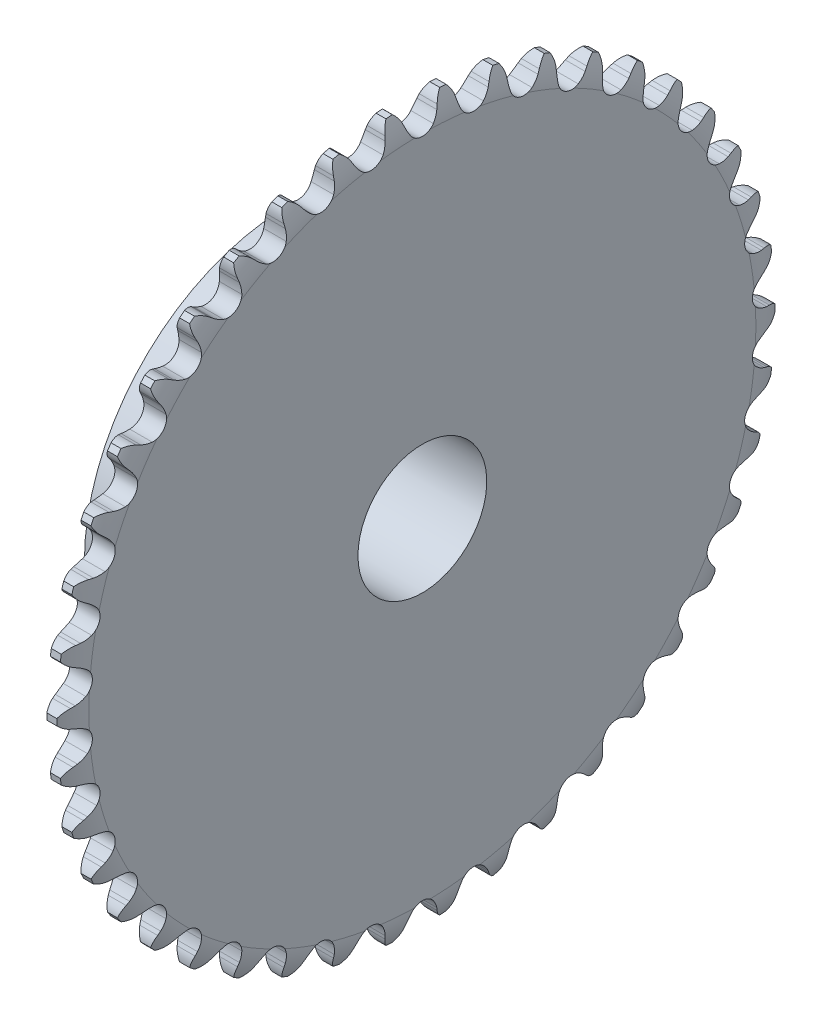
SolidWorks part; units mm, degrees
ref_plane "Plane1" through (0, 0, 0) normal (0, 0, 1) x (1, 0, 0)
ref_plane "Plane2" through (0, 0, 0) normal (0, 1, 0) x (1, 0, 0)
ref_plane "Plane3" through (0, 0, 0) normal (1, 0, 0) x (0, 0, -1)
sketch "Clipboard" plane through (0, 0, 0) normal (0, 1, 0) x (1, 0, 0)
  line L0 (0, 0) -> (4.719, -4.249)
  line L1 (-15, 0) -> (100, 0) construction
  line L2 (0, 0) -> (-0.5218, 0.5897)
  line L3 (0, 0) -> (-2.9658, 1.1335)
  line L4 (0, 0) -> (2.3595, 2.1245)
  line L5 (0, 0) -> (-15.2311, -5.6808)
  line L6 (0, 0) -> (-2.3214, -1.5662)
  line L7 (-0.5218, 0.5897) -> (11.3674, 11.6765)
  line L8 (-76.2, 38.1) -> (-58.1914, 38.1)
  line L9 (-73.2057, 38.5609) -> (-73.0533, 38.5634)
  line L10 (-73.0533, 76.1892) -> (-66.6525, 76.1892)
  circle A0 centre (0, 0) radius 1.651
  circle A1 centre (0, 0) radius 25.4
  circle A2 centre (0, 0) radius 25.4
  dimension "Dr" = 3.302
  dimension "MHD" = 50.8
  dimension "Hub_dia" = 50.8
  dimension "Num_teeth" = 42
  dimension "Pitch" = 6.35
  dimension "Width" = 3.175
  dimension "Chamfer_wid" = 0.7874
  dimension "Chamfer_dep" = 3.175
  dimension "Overall_len" = 16.256
  dimension "Show_teeth" = 42
  dimension "Thickness" = 2.8004
  dimension "OAL" = 16.2564
  dimension "T_dim" = 18.0086
  dimension "Width_const" = 0.1524
  dimension "Width_factor" = 0.93
  dimension "Num_strands" = 1
  dimension "Transv_pitch" = 6.4008
sketch "BasProSke" plane through (0, 0, 0) normal (0, 1, 0) x (1, 0, 0)
  line L0 (-10, 0) -> (60, 0) construction
  line L1 (0, 0) -> (0, 41.0974)
  line L2 (0, 0) -> (2.8003, 0)
  line L3 (2.8003, 0) -> (2.8004, 41.0974)
  line L4 (2.0129, 44.2724) -> (0.7874, 44.2724)
  arc A0 (0, 41.0974) -> (0.7874, 44.2724) centre (6.7949, 41.0974) cw
  arc A1 (2.8004, 41.0974) -> (2.0129, 44.2724) centre (-3.9946, 41.0974) ccw
  dimension "D1" = 6.7949
  dimension "G1" = 0.7874
  dimension "G2" = 0.7874
  dimension "H2" = 3.175
  dimension "Diameter" = 88.5449
  dimension "H1" = 3.175
  dimension "Thickness" = 2.8004
revolve "Base-Revolve" add sketch "BasProSke" angle 360 about L0
sketch "GrvSke" plane through (0, 0, 0) normal (0, 1, 0) x (1, 0, 0)
  line L0 (2.8003, 41.0974) -> (2.8003, 38.8114)
  line L1 (2.8003, 38.8114) -> (6.4008, 38.8114)
  line L2 (6.4008, 38.8114) -> (6.4008, 41.0974)
  line L3 (2.0129, 44.2724) -> (7.1882, 44.2724)
  line L4 (4.6006, 0) -> (4.6006, 52.07) construction
  line L5 (-10, 0) -> (60, 0) construction
  line L6 (0, 0) -> (35.56, 0) construction
  arc A0 (6.4008, 41.0974) -> (7.1882, 44.2724) centre (13.1957, 41.0974) cw
  arc A1 (2.8003, 41.0974) -> (2.0129, 44.2724) centre (-3.9946, 41.0974) ccw
  dimension "Diameter" = 88.5449
  dimension "H1" = 3.175
  dimension "Grv_diam" = 77.6229
  dimension "Grv_width" = 3.6004
  dimension "Offset" = 4.6006
  dimension "G1" = 0.7874
revolve "Groove" [suppressed] cut sketch "GrvSke" angle 360 about L6
pattern_linear "Grooves" [suppressed]
sketch "TooCutSke" plane through (0, 0, 0) normal (1, 0, 0) x (0, 0, -1)
  line L0 (1.958, 42.5878) -> (2.1189, 43.0357)
  line L1 (0, 0) -> (0, 107) construction
  line L2 (0, 42.4862) -> (-10, 42.4862) construction
  line L3 (-1.958, 42.5878) -> (-2.1189, 43.0357)
  arc A0 (1.3657, 41.4783) -> (1.958, 42.5878) centre (-2.1254, 44.0549) ccw
  arc A1 (1.3657, 41.4783) -> (-1.3657, 41.4783) centre (0, 42.4862) cw
  arc A2 (2.1189, 43.0357) -> (4.6099, 44.7876) centre (4.6099, 42.1408) cw
  arc A3 (-1.3657, 41.4783) -> (-1.958, 42.5878) centre (2.1254, 44.0549) cw
  arc A4 (-2.1189, 43.0357) -> (-4.6099, 44.7876) centre (-4.6099, 42.1408) ccw
  arc A5 (4.6099, 44.7876) -> (-4.6099, 44.7876) centre (0, 0) ccw
  dimension "R" = 1.6974
  dimension "E" = 4.339
  dimension "F" = 2.6469
  dimension "Pitch_radius" = 42.4862
  dimension "W" = 4.6099
  dimension "V" = 0.3455
  dimension "A" = 36.429
  dimension "B" = 16.667
extrude "ToothCut" cut sketch "TooCutSke" along normal through all
pattern_circular "TeethCuts" count 42 every 8.571 about axis through (-10, 0, 0) along (1, 0, 0) of "ToothCut"
sketch "HubNeaOneSke" plane through (0, 0, 0) normal (-1, 0, 0) x (0, 0, 1)
  circle A0 centre (0, 0) radius 25.4
  dimension "Diameter" = 50.8
extrude "HubNearOne" add sketch "HubNeaOneSke" along normal blind 13.456
sketch "HubNeaBotSke" plane through (0, 0, 0) normal (-1, 0, 0) x (0, 0, 1)
  circle A0 centre (0, 0) radius 25.4
  dimension "Diameter" = 50.8
extrude "HubNearBoth" [suppressed] add sketch "HubNeaBotSke" along normal blind 6.728
ref_plane "FarPln" through (2.8004, 0, 0) normal (1, 0, 0) x (0, 0, -1)
sketch "HubFarSke" plane through (2.8004, 0, 0) normal (1, 0, 0) x (0, 0, -1)
  circle A0 centre (0, 0) radius 25.4
  dimension "Diameter" = 50.8
extrude "HubFar" [suppressed] add sketch "HubFarSke" along normal blind 6.728
sketch "BorSke" plane through (0, 0, 0) normal (1, 0, 0) x (0, 0, -1)
  circle A0 centre (0, 0) radius 7.9375
  dimension "Diameter" = 15.875
extrude "Bore" cut sketch "BorSke" along normal mid plane 32.5127
sketch "KeySke" plane through (0, 0, 0) normal (1, 0, 0) x (0, 0, -1)
  line L0 (-2.3813, 0) -> (-2.3813, 10.0711)
  line L1 (-2.3813, 10.0711) -> (2.3813, 10.0711)
  line L2 (2.3813, 10.0711) -> (2.3813, 0)
  line L3 (0, 0) -> (0, 34) construction
  line L4 (-2.3813, 0) -> (2.3813, 0)
  dimension "Offset" = 10.0711
  dimension "Width" = 4.7625
extrude "Keyway" [suppressed] cut sketch "KeySke" along normal mid plane 32.5127
pattern_circular "Keyway2" [suppressed] count 2 every 90 about axis through (-10, 0, 0) along (1, 0, 0)
equation "\"Num_teeth@Clipboard\" = int( \"Num_teeth@Clipboard\" )"
equation "\"Num_teeth@Clipboard\" = ((sgn( \"Num_teeth@Clipboard\" - 5.0)+1)*( \"Num_teeth@Clipboard\" - 5.0))/2 +5.0"
equation "\"Num_teeth@Clipboard\" = ((sgn( \"Num_teeth@Clipboard\" - 200.0)-1)*( \"Num_teeth@Clipboard\" - 200.0))/-2 +200.0"
equation "\"MHD@Clipboard\" = \"Pitch@Clipboard\" * (1.0 / tan(3.14159265 / \"Num_teeth@Clipboard\" ) - 1.0) - 0.03"
equation "\"Thickness@Clipboard\"  = \"Width@Clipboard\" * \"Width_factor@Clipboard\" - \"Width_const@Clipboard\" + (\"Num_strands@Clipboard\" - 1) * \"Transv_pitch@Clipboard\""
equation "\"OAL@Clipboard\" = \"Thickness@Clipboard\""
equation "\"MHD@Clipboard\" = ((sgn( \"MHD@Clipboard\" - \"Hub_dia@Clipboard\" )-1)*( \"MHD@Clipboard\" - \"Hub_dia@Clipboard\" ))/-2+ \"Hub_dia@Clipboard\""
equation "\"OAL@Clipboard\" = ((sgn( \"OAL@Clipboard\" - \"Overall_len@Clipboard\" )+1)*( \"OAL@Clipboard\" - \"Overall_len@Clipboard\" ))/2 + \"Overall_len@Clipboard\" + 0.000002"
equation "\"Num_teeth@TeethCuts\" = int( \"Show_teeth@Clipboard\" ) + 1"
equation "\"Num_teeth@TeethCuts\" = ((sgn( \"Num_teeth@TeethCuts\" - \"Num_teeth@Clipboard\" )-1)*( \"Num_teeth@TeethCuts\" - \"Num_teeth@Clipboard\" ))/-2+ \"Num_teeth@Clipboard\""
equation "\"Num_teeth@TeethCuts\" = ((sgn( \"Num_teeth@TeethCuts\" - 2.0)+1)*( \"Num_teeth@TeethCuts\" - 2.0))/2 +2.0"
equation "\"Angle@TeethCuts\" = 360.0 / \"Num_teeth@Clipboard\""
equation "\"Pitch_radius@TooCutSke\" = ( \"Pitch@Clipboard\" / 2.0) / sin(3.14159265 / \"Num_teeth@Clipboard\" )  'ma"
equation "\"R@TooCutSke\"  = \"Dr@Clipboard\" * 0.5025 + 0.0015"
equation "\"A@TooCutSke\" = 35.0 + (60.0 / \"Num_teeth@Clipboard\")"
equation "\"E@TooCutSke\"  = \"Dr@Clipboard\" * 1.3025 + 0.0015"
equation "\"B@TooCutSke\"  = 18.0 - (56.0 / \"Num_teeth@Clipboard\" )"
equation "\"W@TooCutSke\" = 1.4 * \"Dr@Clipboard\" * cos(3.14159265 / \"Num_teeth@Clipboard\" )"
equation "\"V@TooCutSke\" = 1.4 * \"Dr@Clipboard\" * sin(3.14159265 / \"Num_teeth@Clipboard\" )"
equation "\"Diameter@BasProSke\" = 2.0 * ( (0.3 * \"Pitch@Clipboard\" ) +  \"Pitch@Clipboard\" / 2.0 / tan(3.14159265 / \"Num_teeth@Clipboard\" ))"
equation "\"Thickness@BasProSke\"  = \"Thickness@Clipboard\""
equation "\"G1@BasProSke\" =  \"Chamfer_wid@Clipboard\""
equation "\"G2@BasProSke\" =  \"Chamfer_wid@Clipboard\""
equation "\"H1@BasProSke\" =  \"Chamfer_dep@Clipboard\""
equation "\"H2@BasProSke\" =  \"Chamfer_dep@Clipboard\""
equation "\"Diameter@GrvSke\" = \"Diameter@BasProSke\""
equation "\"G1@GrvSke\" = \"Chamfer_wid@Clipboard\""
equation "\"H1@GrvSke\" = \"Chamfer_dep@Clipboard\""
equation "\"Grv_diam@GrvSke\" =  \"Pitch@Clipboard\" * (1.0 / tan(3.14159265 / \"Num_teeth@Clipboard\" ) - 1.0) - 0.03"
equation "\"Grv_width@GrvSke\" =  \"Transv_pitch@Clipboard\" - ( \"Width@Clipboard\" * \"Width_factor@Clipboard\" - \"Width_const@Clipboard\" )"
equation "\"Offset@GrvSke\" = \"Grv_width@GrvSke\" / 2.0 + ( \"Width@Clipboard\" * \"Width_factor@Clipboard\" - \"Width_const@Clipboard\" )"
equation "\"Offset@Grooves\" = \"Transv_pitch@Clipboard\""
equation "\"Num_grvs@Grooves\" = \"Num_strands@Clipboard\""
equation "\"Num_grvs@Grooves\" = \"Num_grvs@Grooves\" - 1 * sgn( \"Num_grvs@Grooves\" -1)"
equation "\"Diameter@HubNeaOneSke\" = \"MHD@Clipboard\""
equation "\"Length@HubNearOne\" = \"OAL@Clipboard\" - \"Thickness@BasProSke\""
equation "\"Diameter@HubNeaBotSke\" = \"MHD@Clipboard\""
equation "\"Length@HubNearBoth\" = ( \"OAL@Clipboard\" - \"Thickness@BasProSke\" ) / 2.0"
equation "\"Thickness@FarPln\" = \"Thickness@BasProSke\""
equation "\"Diameter@HubFarSke\" = \"MHD@Clipboard\""
equation "\"Length@HubFar\" = ( \"OAL@Clipboard\" - \"Thickness@BasProSke\" ) / 2.0"
equation "\"D1@Bore\" = \"OAL@Clipboard\" * 2.0"
equation "\"D1@Keyway\" = \"OAL@Clipboard\" * 2.0"
equation "\"Offset@KeySke\" = \"T_dim@Clipboard\" - \"Diameter@BorSke\" / 2.0"
